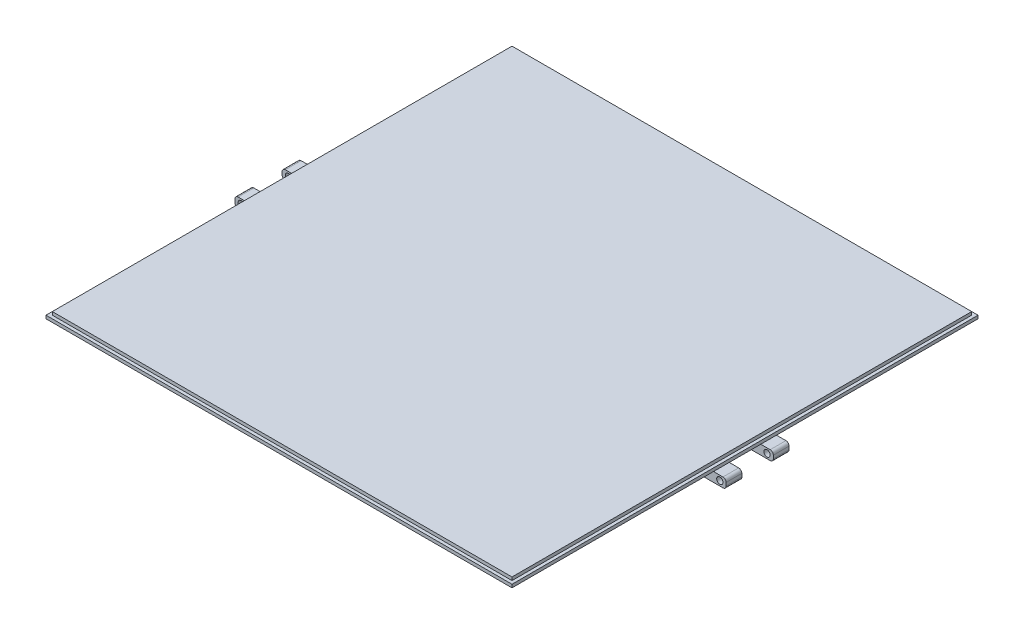
SolidWorks part; units mm, degrees
note: The reader was unsure of these and kept them because the rebuilt part matched: shared geometry of "Sketch6<2>".
material "A286 Iron Base Superalloy"
ref_plane "Front Plane" through (0, 0, 0) normal (0, 0, 1) x (1, 0, 0)
ref_plane "Top Plane" through (0, 0, 0) normal (0, 1, 0) x (1, 0, 0)
ref_plane "Right Plane" through (0, 0, 0) normal (1, 0, 0) x (0, 0, -1)
sketch "Sketch1" plane through (0, 0, 0) normal (0, 1, 0) x (1, 0, 0)
  circle A0 centre (0, 0) radius 10
  circle A2 centre (0, 0) radius 7.5
  dimension "D1" = 20
  dimension "D2" = 15
extrude "Boss-Extrude1" add sketch "Sketch1" along normal blind 25
thread "Thread1" pitch 0.3175 start angle 0, offset 0.5, length 6, pitch 0.3175, diameter 20
ref_plane "Plane1" through (10, -0.5, 0) normal (0, 0, 1) x (1, 0, 0)
sketch "Thread Profile1" plane through (10, -0.5, 0) normal (0, 0, 1) x (1, 0, 0)
  line L0 (0, 0) -> (0, 0.3175) construction
  line L11 (0, 0) -> (0, 0.2778)
  line L12 (0, 0.2778) -> (-0.1719, 0.1786)
  line L13 (-0.1719, 0.1786) -> (-0.1719, 0.0992)
  line L15 (-0.1719, 0.0992) -> (0, 0)
  line L17 (-0.1719, 0.1389) -> (0, 0.1389) construction
  point P2 (0, 0)
  dimension "Pitch" = 0.3175
  dimension "Profile_Angle" = 60
  dimension "Profile_Land" = 0.0794
  dimension "Profile_Height" = 0.1719
sketch "Sketch4" plane through (0, 25, 0) normal (0, 1, 0) x (1, 0, 0)
  line L0 (0, 0) -> (73, 0) construction
  line L1 (73, 0) -> (73, -73) construction
  line L3 (73, -73) -> (-73, -73)
  line L4 (73, -73) -> (73, 73)
  line L5 (73, 73) -> (-73, 73)
  line L6 (-73, -73) -> (-73, 73)
  dimension "D1" = 73
  dimension "D2" = 73
  dimension "D3" = 146
  dimension "D4" = 146
  dimension "D5" = 73
extrude "Boss-Extrude2" add sketch "Sketch4" along normal blind 2
sketch "Sketch5" plane through (0, 25, 0) normal (0, -1, 0) x (1, 0, 0)
  line L0 (-73, -73) -> (-73, 73) construction
  line L1 (-74, 74) -> (74, 74)
  line L2 (-74, 74) -> (-74, -74)
  line L3 (-74, -74) -> (74, -74)
  line L4 (74, 74) -> (74, -74)
  line L5 (73, -73) -> (-73, -73) construction
  dimension "D1" = 148
  dimension "D2" = 148
  dimension "D3" = 1
  dimension "D4" = 1
extrude "Boss-Extrude3" add sketch "Sketch5" against normal blind 1
sketch "Sketch6" plane through (0, 0, 0) normal (0, 0, 1) x (1, 0, 0)
  line L0 (74, 25) -> (-74, 25) construction
  line L1 (68, 25) -> (78, 25)
  line L2 (68, 25) -> (68, 22)
  line L3 (68, 22) -> (78, 22)
  line L4 (78, 25) -> (78, 22)
  line L5 (0, 0) -> (0, 25) construction
  line L6 (-10, 25) -> (10, 25) construction
  line L7 (-68, 25) -> (-68, 22)
  line L8 (-68, 22) -> (-78, 22)
  line L9 (-78, 25) -> (-78, 22)
  line L10 (-68, 25) -> (-78, 25)
  circle A0 centre (76, 23.5) radius 1
  circle A1 centre (-76, 23.5) radius 1
  dimension "D4" = 2
  dimension "D1" = 3
  dimension "D2" = 10
  dimension "D3" = 6
  dimension "D5" = 2
  dimension "D6" = 1.5
extrude "Boss-Extrude4" add sketch "Sketch6" along normal mid plane 5 from offset 7.5
extrude "Boss-Extrude5" add sketch "Sketch6<2>" along normal mid plane 5 from offset 7.5 offset against normal yes
sketch "Sketch6<2>" plane through (0, 0, 0) normal (0, 0, 1) x (1, 0, 0) same geometry as "Sketch6"
sketch "Sketch9" plane through (0, 25, 0) normal (0, -1, 0) x (1, 0, 0)
  circle A0 centre (0, 0) radius 18.9956
extrude "Cut-Extrude1" cut sketch "Sketch9" along normal through all
chamfer "Chamfer1" distance 3 angle 45 4 edges at (68, 25, -7.5) (68, 25, 7.5) (-68, 25, -7.5) (-68, 25, 7.5)
fillet "Fillet1" radius 1 8 edges at (78, 25, -7.5) (78, 22, -7.5) (78, 22, 7.5) (78, 25, 7.5) (-78, 22, 7.5) (-78, 25, 7.5) (-78, 22, -7.5) (-78, 25, -7.5)
